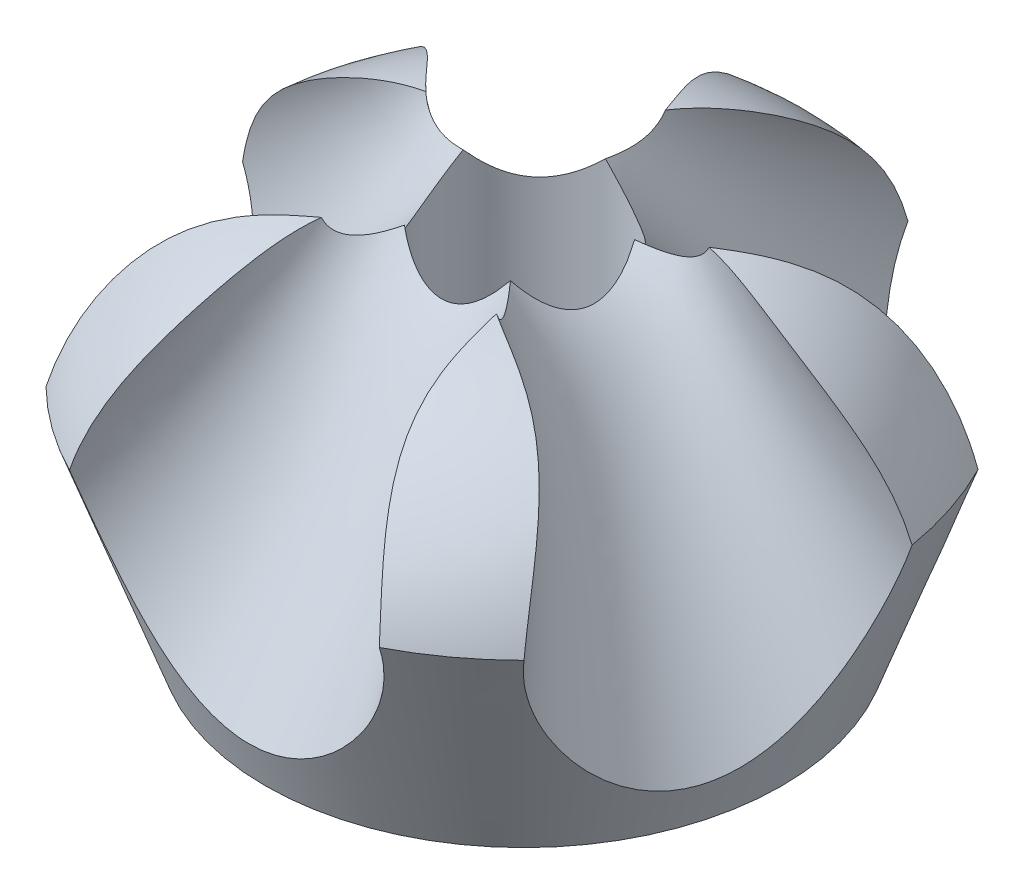
SolidWorks part; units mm, degrees
ref_plane "Front Plane" through (0, 0, 0) normal (0, 0, 1) x (1, 0, 0)
ref_plane "Top Plane" through (0, 0, 0) normal (0, 1, 0) x (1, 0, 0)
ref_plane "Right Plane" through (0, 0, 0) normal (1, 0, 0) x (0, 0, -1)
sketch "Sketch1" plane through (0, 0, 0) normal (0, 0, 1) x (1, 0, 0)
  line L0 (0, 0) -> (-15, 0)
  line L1 (-15, 0) -> (-19.6173, 12.6859)
  line L5 (0, 13) -> (0, 0)
  line L8 (0, 13) -> (0, 20.2524)
  arc A4 (-19.6173, 12.6859) -> (0, 20.2524) centre (-6.9751, 9.1227) cw
  point P8 (0, 27.7517)
  dimension "D1" = 15
  dimension "D2" = 13
  dimension "D3" = 13.5
  dimension "D6" = 110
revolve "Revolve1" add sketch "Sketch1" angle 360 about L5
ref_plane "Plane1" through (0, -4.8209, 13.2453) normal (0, -0.342, 0.9397) x (1, 0, 0)
sketch "Sketch4" plane through (0, -4.8209, 13.2453) normal (0, -0.342, 0.9397) x (1, 0, 0)
  circle A44 centre (0, 17.7606) radius 9.8847
sketch3d "3DSketch1"
  point P4 (0, 27.7517, 0)
sketch "Sketch5" plane through (0, 0, 0) normal (0, 1, 0) x (1, 0, 0)
  line L1 (3.5355, 3.5355) -> (-3.5355, 3.5355) construction
  line L2 (3.5355, 3.5355) -> (3.5355, -3.5355) construction
  line L3 (3.5355, -3.5355) -> (-3.5355, -3.5355) construction
  line L4 (-3.5355, 3.5355) -> (-3.5355, -3.5355) construction
  line L5 (3.5355, 3.5355) -> (-3.5355, -3.5355) construction
  line L6 (3.5355, -3.5355) -> (-3.5355, 3.5355) construction
  circle A0 centre (0, 0) radius 5
  dimension "D1" = 10
sketch "Sketch6" plane through (0, 0, 0) normal (0, 1, 0) x (1, 0, 0)
  line L0 (0, 7.435) -> (0, -7.1989) construction
sketch "Sketch9" plane through (0, 0, 0) normal (0, 0, 1) x (1, 0, 0)
  circle A2 centre (0, 29.5835) radius 6.4357
loft "Cut-Loft1" cut profiles "Sketch9", "Sketch4" connector at (6.377, 30.4502, 0) connector at (0, 2.5801, 15.9391)
pattern_circular "CirPattern1" count 5 over 360 about axis through (0, 12.6859, 0) along (0, -1, 0) of "Cut-Loft1"
sketch "Sketch10" plane through (0, 0, 0) normal (0, 1, 0) x (1, 0, 0)
  line L1 (13.8715, -13.8715) -> (-13.8715, -13.8715)
  line L2 (13.8715, -13.8715) -> (13.8715, 13.8715)
  line L3 (13.8715, 13.8715) -> (-13.8715, 13.8715)
  line L4 (-13.8715, -13.8715) -> (-13.8715, 13.8715)
  line L5 (13.8715, -13.8715) -> (-13.8715, 13.8715) construction
  line L6 (13.8715, 13.8715) -> (-13.8715, -13.8715) construction
  circle A0 centre (0, 0) radius 19.6173 construction
sketch "Sketch11" plane through (0, 0, 0) normal (0, 1, 0) x (1, 0, 0)
  line L0 (3.5355, -3.5355) -> (-3.5355, 3.5355) construction
  circle A0 centre (0, 0) radius 1.7
  dimension "D1" = 3.4
extrude "Cut-Extrude2" cut sketch "Sketch11" along normal blind 10 and the other way through all
sketch "Sketch13" plane through (0, 10, 0) normal (0, -1, 0) x (1, 0, 0)
  circle A0 centre (0, 0) radius 5
  dimension "D1" = 10
extrude "Cut-Extrude3" cut sketch "Sketch13" against normal through all
